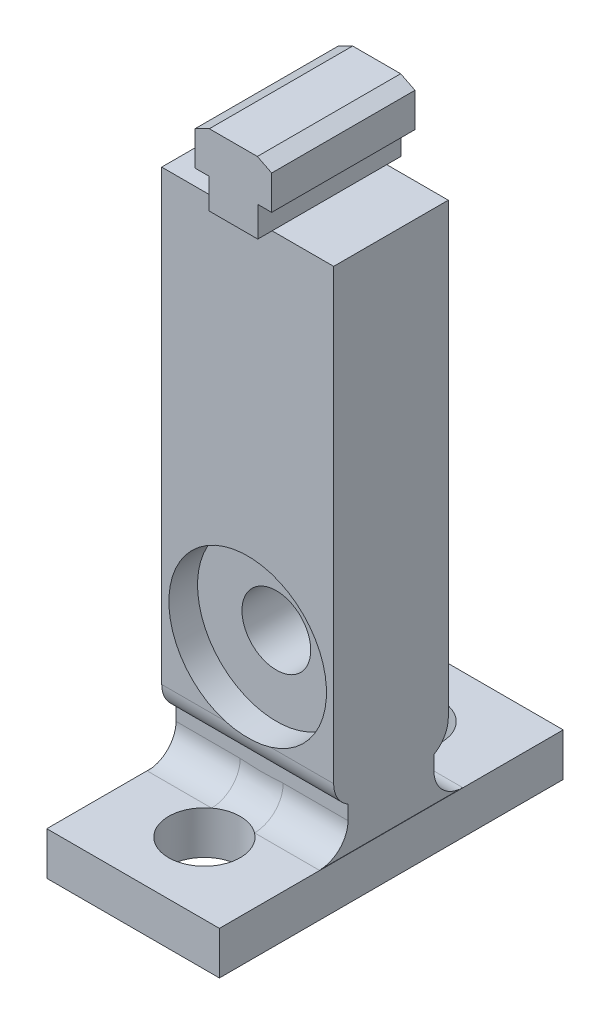
SolidWorks part; units mm, degrees
ref_plane "Front Plane" through (0, 0, 0) normal (0, 0, 1) x (1, 0, 0)
ref_plane "Top Plane" through (0, 0, 0) normal (0, 1, 0) x (1, 0, 0)
ref_plane "Right Plane" through (0, 0, 0) normal (1, 0, 0) x (0, 0, -1)
sketch "Sketch1" plane through (0, 0, 0) normal (0, 0, 1) x (1, 0, 0)
  line L0 (-2.695, 0.5997) -> (-1.695, 1.0997)
  line L1 (-2.695, -1.7803) -> (-1.715, -1.7803)
  line L2 (-2.695, -1.7803) -> (-2.695, 0.5997)
  line L3 (-1.695, 1.0997) -> (1.655, 1.0997)
  line L4 (2.655, -1.7803) -> (2.655, 0.5997)
  line L7 (2.655, 0.5997) -> (1.655, 1.0997)
  line L8 (1.685, -1.7803) -> (2.655, -1.7803)
  line L10 (-1.715, -1.7803) -> (-1.715, -3.8803)
  line L11 (-1.715, -3.8803) -> (1.685, -3.8803)
  line L12 (1.685, -1.7803) -> (1.685, -3.8803)
  point P0 (0, 0)
  dimension "D1" = 5.35
  dimension "D2" = 3.4
  dimension "D3" = 2.1
  dimension "2.38" = 2.38
  dimension "D5" = 2.38
  dimension "D6" = 0.5
  dimension "D7" = 1
  dimension "D8" = 1
  dimension "D9" = 0.97
extrude "Boss-Extrude1" add sketch "Sketch1" along normal blind 10
sketch "Sketch3" plane through (0, -3.8803, 0) normal (0, -1, 0) x (1, 0, 0)
  line L0 (-1.695, 10) -> (1.655, 0)
  line L2 (-6.02, 3) -> (5.98, 3)
  line L3 (-6.02, 3) -> (-6.02, 7)
  line L4 (-6.02, 7) -> (5.98, 7)
  line L5 (5.98, 3) -> (5.98, 7)
  line L6 (-6.02, 3) -> (5.98, 7) construction
  line L7 (-6.02, 7) -> (5.98, 3) construction
  point P4 (-0.02, 5)
  line M6 (1.685, 0) -> (1.685, 10)
  line M8 (-1.715, 10) -> (-1.715, 0)
  dimension "D1" = 12
  dimension "D2" = 4
extrude "Boss-Extrude2" add sketch "Sketch3" along normal blind 36 contours L4 L3 L2 M8 | L4 L2 L0 M8 | L4 L0 L2 M6 | L2 L5 L4 M6 region at (0.7886, -3.8803, 5.262) region at (-0.8234, -3.8803, 4.7365) region at (-3.8675, -3.8803, 5) region at (3.8325, -3.8803, 5)
sketch "Sketch4" plane through (0, 0, 7) normal (0, 0, 1) x (1, 0, 0)
  line L0 (-6.02, -3.8803) -> (-1.715, -3.8803) construction
  line L1 (5.98, -39.8803) -> (5.98, -3.8803) construction
  line L2 (5.98, -21.8803) -> (-6.02, -37.8803) construction
  line L3 (-6.02, -39.8803) -> (-6.02, -3.8803) construction
  circle A0 centre (-0.02, -29.8803) radius 2.4
  dimension "D1" = 4.8
  dimension "D2" = 26
extrude "Cut-Extrude1" cut sketch "Sketch4" against normal blind 8
sketch "Sketch6" plane through (0, 0, 7) normal (0, 0, 1) x (1, 0, 0)
  line L10 (-1.715, -3.8803) -> (-6.02, -3.8803)
  line L11 (-6.02, -3.8803) -> (-6.02, -39.8803)
  line L12 (-6.02, -39.8803) -> (5.98, -39.8803)
  line L13 (5.98, -39.8803) -> (5.98, -3.8803)
  line L14 (5.98, -3.8803) -> (1.685, -3.8803)
  line L15 (1.685, -3.8803) -> (-1.715, -3.8803)
  line L18 (-1.715, -3.8803) -> (-6.02, -3.8803)
  line L19 (-6.02, -3.8803) -> (-6.02, -39.8803)
  line L20 (-6.02, -39.8803) -> (5.98, -39.8803)
  line L21 (5.98, -39.8803) -> (5.98, -3.8803)
  line L22 (5.98, -3.8803) -> (1.685, -3.8803)
  line L24 (1.685, -3.8803) -> (-1.715, -3.8803)
  circle A0 centre (-0.02, -29.8803) radius 5.5
  dimension "D2" = 11
  dimension "D1" = 0
extrude "Boss-Extrude7" add sketch "Sketch6" along normal blind 2
extrude "Boss-Extrude8" add sketch "Sketch6<2>" against normal blind 6
sketch "Sketch6<2>" plane through (0, 0, 7) normal (0, 0, 1) x (1, 0, 0) same geometry as "Sketch6"
sketch "Sketch9" plane through (0, -39.8803, 0) normal (0, -1, 0) x (1, 0, 0)
  line L0 (-6.02, 9) -> (5.98, 1) construction
  line L1 (5.98, 1) -> (-6.02, 1) construction
  line L2 (-6.02, 1) -> (5.98, 9) construction
  line L4 (-6.0437, -6.9972) -> (6.0037, -6.9972)
  line L5 (-6.0437, -6.9972) -> (-6.0437, 16.9972)
  line L6 (-6.0437, 16.9972) -> (6.0037, 16.9972)
  line L7 (6.0037, -6.9972) -> (6.0037, 16.9972)
  line L8 (-6.0437, -6.9972) -> (6.0037, 16.9972) construction
  line L9 (-6.0437, 16.9972) -> (6.0037, -6.9972) construction
  circle A0 centre (-0.04, 12) radius 2.5
  circle A1 centre (0, -2) radius 2.5
  point P4 (-0.02, 5)
  dimension "D1" = 5
  dimension "D2" = 5
  dimension "D3" = 14
  dimension "D4" = 7
  dimension "D5" = 7
extrude "Boss-Extrude10" add sketch "Sketch9" along normal blind 3
sketch "Sketch10" plane through (5.98, 0, 0) normal (1, 0, 0) x (0, 0, -1)
  line L0 (6.9972, -39.8803) -> (-16.9972, -39.8803) construction
  line L1 (6.9972, -39.8803) -> (-16.9972, -39.8803)
  line L3 (-9, -39.8803) -> (-8, -39.8803)
  line L4 (-9, -3.8803) -> (-9, -39.8803)
  line L5 (-9, -39.8803) -> (-1, -39.8803)
  line L6 (-1, -39.8803) -> (-1, -3.8803)
  line L7 (-1, -3.8803) -> (-9, -3.8803)
  line L8 (-9, -3.8803) -> (-9, -39.8803)
  line L9 (-9, -39.8803) -> (-1, -39.8803)
  line L10 (-1, -39.8803) -> (-1, -3.8803)
  line L11 (-1, -3.8803) -> (-9, -3.8803)
  line L12 (-9, -39.8803) -> (-9, -36.8803)
  line L13 (-9, -36.8803) -> (-8, -36.8803)
  line L14 (-8, -39.8803) -> (-8, -36.8803)
  line L15 (-1, -39.8803) -> (-2, -39.8803)
  line L16 (-1, -39.8803) -> (-1, -36.8803)
  line L17 (-1, -36.8803) -> (-2, -36.8803)
  line L18 (-2, -39.8803) -> (-2, -36.8803)
  line M10 (-9, -39.8803) -> (-1, -39.8803)
  line M11 (-1, -39.8803) -> (-1, -3.8803)
  dimension "D2" = 1
  dimension "D3" = 3
  dimension "D4" = 1
  dimension "D5" = 3
  dimension "D1" = 0
extrude "Cut-Extrude2" cut sketch "Sketch10" against normal up to surface (12 mm away) contours L14 L13 L8 M10 | L18 L9 L17 M11 region at (5.98, -38.3803, 1.5) region at (5.98, -38.3803, 8.5) up to face at (-6.02, -21.8803, 5)
fillet "Fillet1" radius 2 4 edges at (-0.02, -36.8803, 1) (-0.02, -39.8803, 2) (-0.02, -39.8803, 8) (-0.02, -36.8803, 9)
